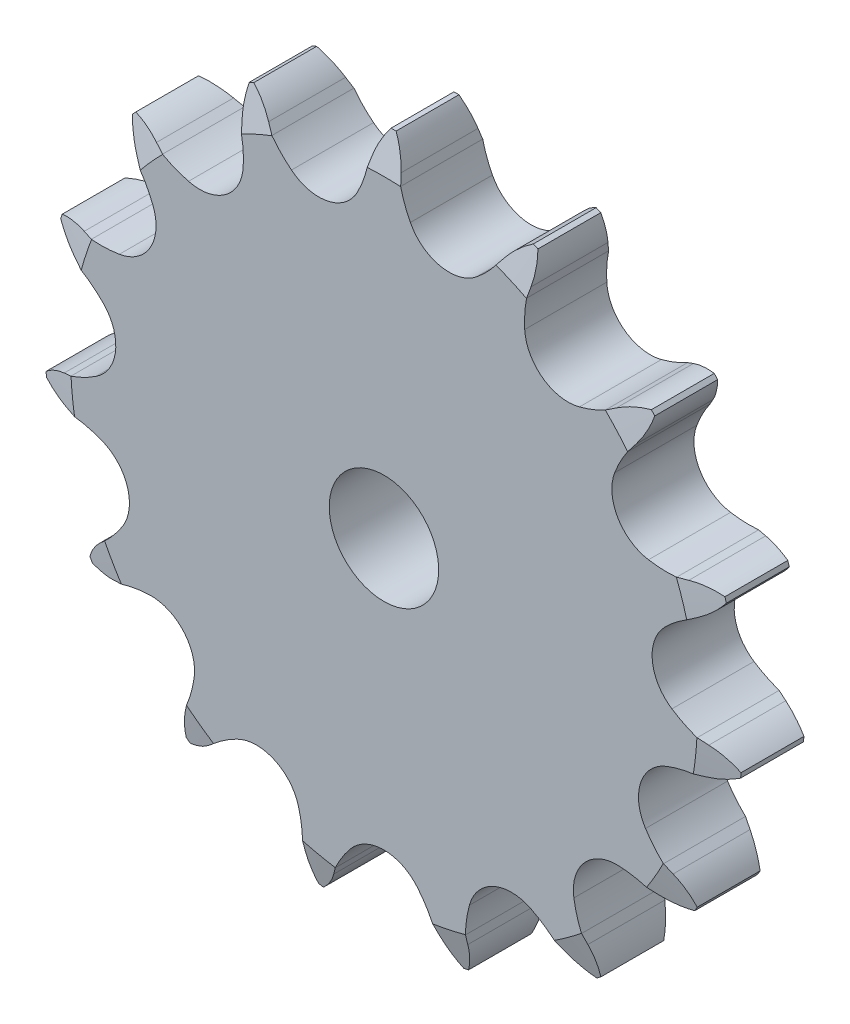
SolidWorks part; units mm, degrees
ref_plane "Front Plane" through (0, 0, 0) normal (0, 0, 1) x (1, 0, 0)
ref_plane "Top Plane" through (0, 0, 0) normal (0, 1, 0) x (1, 0, 0)
ref_plane "Right Plane" through (0, 0, 0) normal (1, 0, 0) x (0, 0, -1)
sketch "Sketch1" plane through (0, 0, 0) normal (0, 0, 1) x (1, 0, 0)
  line L3 (0, 0) -> (0, 54.4723) construction
  line L4 (-44.2979, 22.9064) -> (42.9505, 22.9064) construction
  line L5 (3.9479, 39.4826) -> (3.9479, 22.7186) construction
  line L6 (-19.6613, 26.1033) -> (20.7308, 26.1033) construction
  line L7 (3.9479, 26.1033) -> (-8.6727, 15.8833) construction
  line L8 (3.9479, 26.1033) -> (-3.5656, 22.6422) construction
  line L9 (-3.5656, 22.6422) -> (-6.4779, 28.9642) construction
  line L10 (-8.6957, 36.9773) -> (-8.6957, 20.618) construction
  line L11 (-19.962, 21.058) -> (23.9482, 21.058) construction
  line L12 (0, 0) -> (-9.3983, 44.2157) construction
  line L13 (-3.5656, 22.6422) -> (-3.8617, 23.2849) construction
  line L14 (3.5656, 22.6422) -> (3.8617, 23.2849) construction
  line L59 (0, 0) -> (0, -15) construction
  circle A0 centre (0, 0) radius 4 construction
  circle A2 centre (0, 0) radius 25.527 construction
  circle A8 centre (0, 0) radius 22.9064 construction
  circle A9 centre (0, 22.9064) radius 3.1781 construction
  arc A10 (-3.5656, 22.6422) -> (-2.4698, 20.9063) centre (3.9234, 26.1559) ccw construction
  circle A11 centre (-8.6957, 21.058) radius 5.3223 construction
  arc A12 (2.4698, 20.9063) -> (-2.4698, 20.9063) centre (0, 22.9064) cw construction
  arc A13 (-2.4698, 20.9063) -> (-3.5656, 22.6422) centre (3.9234, 26.1559) cw construction
  arc A14 (-3.8617, 23.2849) -> (-5.357, 25.2029) centre (-8.6957, 21.058) ccw construction
  arc A15 (2.4698, 20.9063) -> (3.5656, 22.6422) centre (-3.9234, 26.1559) ccw construction
  arc A16 (3.8617, 23.2849) -> (5.357, 25.2029) centre (8.6957, 21.058) cw construction
  arc A127 (-5.357, 25.2029) -> (5.357, 25.2029) centre (0, 22.9064) cw construction
  point P24 (3.9479, 26.1033)
  point P27 (0, 22.9064)
  point P38 (-5.357, 25.2029)
  point P339 (0, 0)
sketch "Sketch2" plane through (0, 0, 0) normal (1, 0, 0) x (0, 0, -1)
  line L1 (-3, 4) -> (3, 4) construction
  line L3 (-3, -25.527) -> (3, -25.527) construction
  line L4 (-3, 25.527) -> (3, 25.527) construction
  line L11 (-3, 0) -> (3, 0) construction
  point P4 (0, 4)
  point P6 (0, 25.527)
  point P10 (0, -25.527)
  point P14 (0, 0)
  dimension "O'all Width" = 6
sketch "Sketch3" plane through (0, 0, 0) normal (1, 0, 0) x (0, 0, -1)
  line L0 (-3, 25.527) -> (3, 25.527) construction
  line L1 (-3, 4) -> (3, 4)
  line L2 (-3, 4) -> (-3, 25.527)
  line L3 (-3, 25.527) -> (3, 25.527)
  line L4 (3, 4) -> (3, 25.527)
  line L5 (-3, 4) -> (3, 4) construction
revolve "Revolve5" add sketch "Sketch3" angle 360 about L11
sketch "Sketch4" plane through (0, 0, 0) normal (0, 0, 1) x (1, 0, 0)
  line L0 (-3.5656, 22.6422) -> (-3.8617, 23.2849) construction
  line L1 (1.2199, 22.8887) -> (1.0639, 23.5789)
  line L2 (-3.5656, 22.6422) -> (-3.8617, 23.2849) construction
  line L4 (3.5656, 22.6422) -> (3.8617, 23.2849) construction
  line L5 (3.5656, 22.6422) -> (3.8617, 23.2849) construction
  line L6 (0, 0) -> (0, 25.527) construction
  line L9 (8.1953, 21.4061) -> (8.6185, 21.9731)
  line L10 (0, 0) -> (4.7625, 22.4058) construction
  line L11 (0, 0) -> (-4.7625, 22.4058) construction
  arc A0 (-3.8617, 23.2849) -> (-5.357, 25.2029) centre (-8.6957, 21.058) ccw construction
  arc A1 (-3.5656, 22.6422) -> (-2.4698, 20.9063) centre (3.9234, 26.1559) ccw construction
  arc A2 (-2.4698, 20.9063) -> (2.4698, 20.9063) centre (0, 22.9064) ccw construction
  circle A3 centre (0, 0) radius 25.527 construction
  arc A6 (-3.8617, 23.2849) -> (-5.357, 25.2029) centre (-8.6957, 21.058) ccw construction
  arc A7 (-3.5656, 22.6422) -> (-2.4698, 20.9063) centre (3.9234, 26.1559) ccw construction
  arc A8 (-2.4698, 20.9063) -> (2.4698, 20.9063) centre (0, 22.9064) ccw construction
  arc A12 (2.4698, 20.9063) -> (3.5656, 22.6422) centre (-3.9234, 26.1559) ccw construction
  arc A13 (5.357, 25.2029) -> (3.8617, 23.2849) centre (8.6957, 21.058) ccw construction
  arc A14 (5.357, 25.2029) -> (-5.357, 25.2029) centre (0, 22.9064) ccw construction
  arc A15 (2.4698, 20.9063) -> (3.5656, 22.6422) centre (-3.9234, 26.1559) ccw construction
  arc A16 (5.357, 25.2029) -> (3.8617, 23.2849) centre (8.6957, 21.058) ccw construction
  arc A17 (5.357, 25.2029) -> (-5.357, 25.2029) centre (0, 22.9064) ccw construction
  arc A23 (10.48, 23.5384) -> (0, 25.766) centre (4.7625, 22.4058) ccw
  arc A24 (1.0639, 23.5789) -> (0, 25.766) centre (-4.1275, 22.4058) ccw
  arc A25 (1.2199, 22.8887) -> (1.9308, 20.963) centre (9.2758, 24.7686) ccw
  arc A26 (1.9308, 20.963) -> (6.7625, 19.936) centre (4.7625, 22.4058) ccw
  arc A27 (6.7625, 19.936) -> (8.1953, 21.4061) centre (1.6004, 26.4001) ccw
  arc A28 (10.48, 23.5384) -> (8.6185, 21.9731) centre (12.8839, 18.7899) ccw
  circle A29 centre (0, 0) radius 22.9064 construction
  circle A30 centre (0, 0) radius 28.7349 construction
  dimension "D2" = 12
  dimension "D4" = 24.733
  dimension "D5" = 24.733
  dimension "D1" = 12
  dimension "D3" = 2
extrude "Cut-Extrude4" cut sketch "Sketch4" against normal through all both and the other way through all
pattern_circular "CirPattern2" count 15 over 360 about axis through (0, 0, 3) along (0, 0, -1) of "Cut-Extrude4"
sketch "Sketch5" plane through (0, 0, 3) normal (0, 0, 1) x (1, 0, 0)
  circle A0 centre (0, 0) radius 22.9064 construction
  circle A1 centre (0, 0) radius 22.9064
extrude "Cut-Extrude5" cut sketch "Sketch5" against normal through all draft 75 flip side to cut
sketch "Sketch6" plane through (0, 0, -3) normal (0, 0, -1) x (-1, 0, 0)
  circle A1 centre (0, 0) radius 22.9064
  circle A2 centre (0, 0) radius 22.9064
  dimension "D1" = 0
extrude "Cut-Extrude6" cut sketch "Sketch6" against normal through all draft 75 flip side to cut
sketch "Sketch7" plane through (0, 0, 0) normal (0, 0, 1) x (1, 0, 0)
  point P0 (4.7625, 22.4058)
  point P1 (-4.7625, 22.4058)
ref_axis "Center Axis 1" through (0, 0, -3) along (0, 0, 1)
ref_axis "Center Axis 2" through (4.7625, 22.4058, -21.9306) along (0, 0, 1)
ref_axis "Center Axis 3" through (-4.7625, 22.4058, -22.0643) along (0, 0, 1)
equation "\"D1@Sketch1\"=\"E@Sketch1\""
equation "\"No. of Teeth@CirPattern2\"=\"No. of Teeth@Sketch1\""
equation "\"D2@Sketch4\"=(360/\"No. of Teeth@Sketch1\")*.5"
equation "\"D5@Sketch4\"=\"D4@Sketch4\""
equation "\"D1@Sketch4\"=\"D2@Sketch4\""
